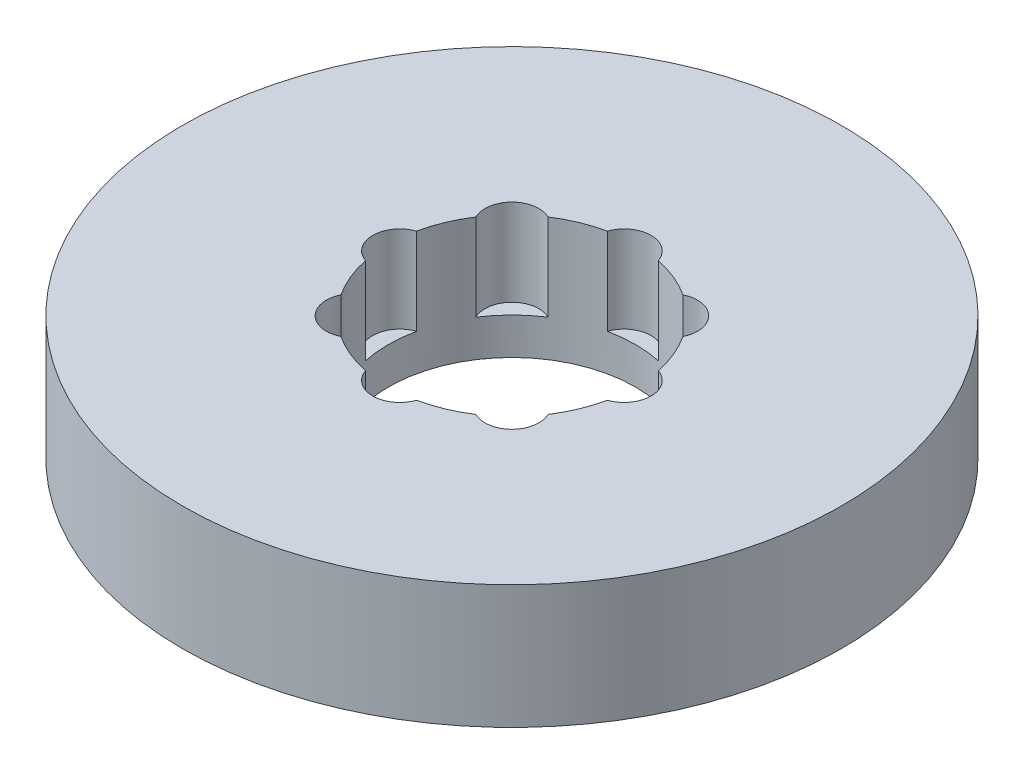
SolidWorks part; units mm, degrees
ref_plane "Front Plane" through (0, 0, 0) normal (0, 0, 1) x (1, 0, 0)
ref_plane "Top Plane" through (0, 0, 0) normal (0, 1, 0) x (1, 0, 0)
ref_plane "Right Plane" through (0, 0, 0) normal (1, 0, 0) x (0, 0, -1)
sketch "Sketch1" plane through (0, 0, 0) normal (0, 1, 0) x (1, 0, 0)
  circle A0 centre (0, 0) radius 40
  dimension "FLANGE_OD" = 80
extrude "Boss-Extrude1" add sketch "Sketch1" along normal blind 15
sketch "Sketch2" plane through (0, 0, 0) normal (0, 1, 0) x (1, 0, 0)
  circle A0 centre (0, 0) radius 15
  dimension "BORE_D" = 30
extrude "Cut-Extrude1" cut sketch "Sketch2" along normal through all
sketch "Sketch3" plane through (0, 15, 0) normal (0, 1, 0) x (1, 0, 0)
  circle A0 centre (0, 0) radius 13.6181 construction
  circle A1 centre (-13.6181, 0) radius 3.2723
  dimension "BOLT_D" = 6.5446
  dimension "BOLT_PCD" = 27.2363
extrude "Cut-Extrude2" cut sketch "Sketch3" against normal blind 10.5308
pattern_circular "CirPattern1" count 8 over 360 about axis through (0, 0, 0) along (0, 1, 0) of "Cut-Extrude2"
